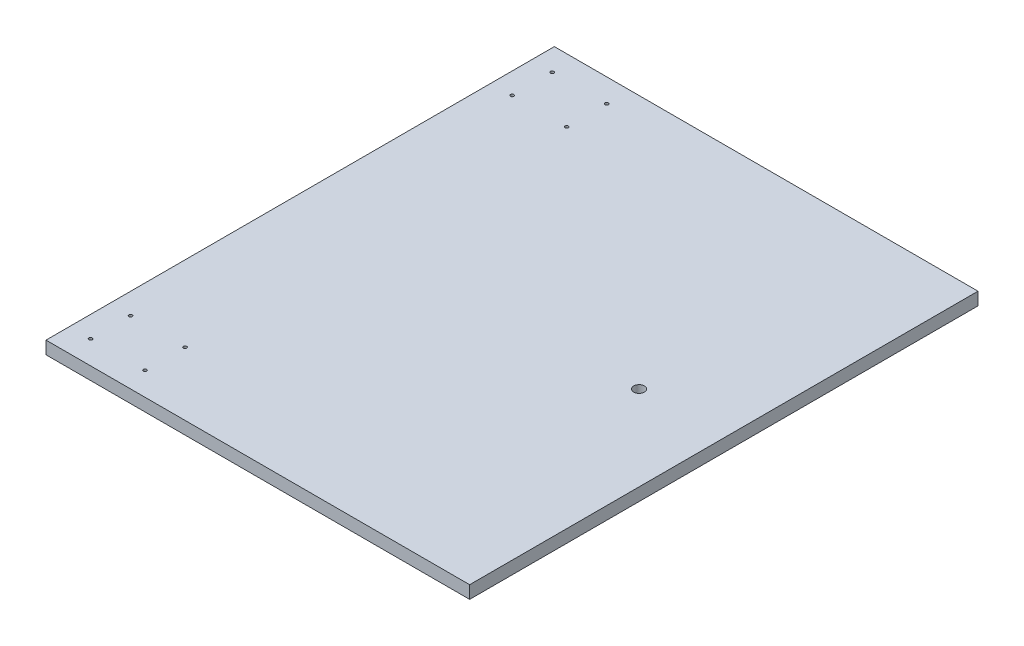
SolidWorks part; units mm, degrees
material "Cedar"
ref_plane "Front" through (0, 0, 0) normal (0, 0, 1) x (1, 0, 0)
ref_plane "Top" through (0, 0, 0) normal (0, 1, 0) x (1, 0, 0)
ref_plane "Right" through (0, 0, 0) normal (1, 0, 0) x (0, 0, -1)
sketch "Sketch1" plane through (0, 0, 0) normal (0, 1, 0) x (1, 0, 0)
  line L1 (-190.5, -228.6) -> (190.5, -228.6)
  line L2 (-190.5, -228.6) -> (-190.5, 228.6)
  line L3 (-190.5, 228.6) -> (190.5, 228.6)
  line L4 (190.5, -228.6) -> (190.5, 228.6)
  line L5 (-190.5, -228.6) -> (190.5, 228.6) construction
  line L6 (-190.5, 228.6) -> (190.5, -228.6) construction
  point P0 (0, 0)
  dimension "D1" = 457.2
  dimension "D2" = 381
extrude "Boss-Extrude1" add sketch "Sketch1" along normal blind 11.4554 contours L1 L4 L3 L2
sketch "Sketch3" plane through (0, 11.4554, 0) normal (0, 1, 0) x (1, 0, 0)
  line L0 (190.5, -228.6) -> (190.5, 228.6) construction
  line L1 (-171.45, 207.6) -> (-171.45, 171.6) construction
  line L2 (-171.45, 171.6) -> (-122.45, 171.6) construction
  line L3 (-122.45, 171.6) -> (-122.45, 207.6) construction
  line L4 (-122.45, 207.6) -> (-171.45, 207.6) construction
  line L5 (-190.5, 228.6) -> (190.5, 228.6) construction
  line L6 (-190.5, -228.6) -> (-190.5, 228.6) construction
  line L7 (130.8452, 0) -> (-366.2568, 0) construction
  circle A0 centre (114.3, 0) radius 4.826
  circle A1 centre (-122.45, 207.6) radius 1.5
  circle A2 centre (-171.45, 207.6) radius 1.5
  circle A3 centre (-171.45, 171.6) radius 1.5
  circle A4 centre (-122.45, 171.6) radius 1.5
  circle A5 centre (-122.45, -171.6) radius 1.5
  circle A6 centre (-171.45, -171.6) radius 1.5
  circle A7 centre (-171.45, -207.6) radius 1.5
  circle A8 centre (-122.45, -207.6) radius 1.5
  dimension "D1" = 9.652
  dimension "D2" = 76.2
  dimension "D3" = 3
  dimension "D4" = 36
  dimension "D5" = 49
  dimension "D6" = 21
  dimension "D7" = 19.05
extrude "Cut-Extrude1" cut sketch "Sketch3" against normal through all
